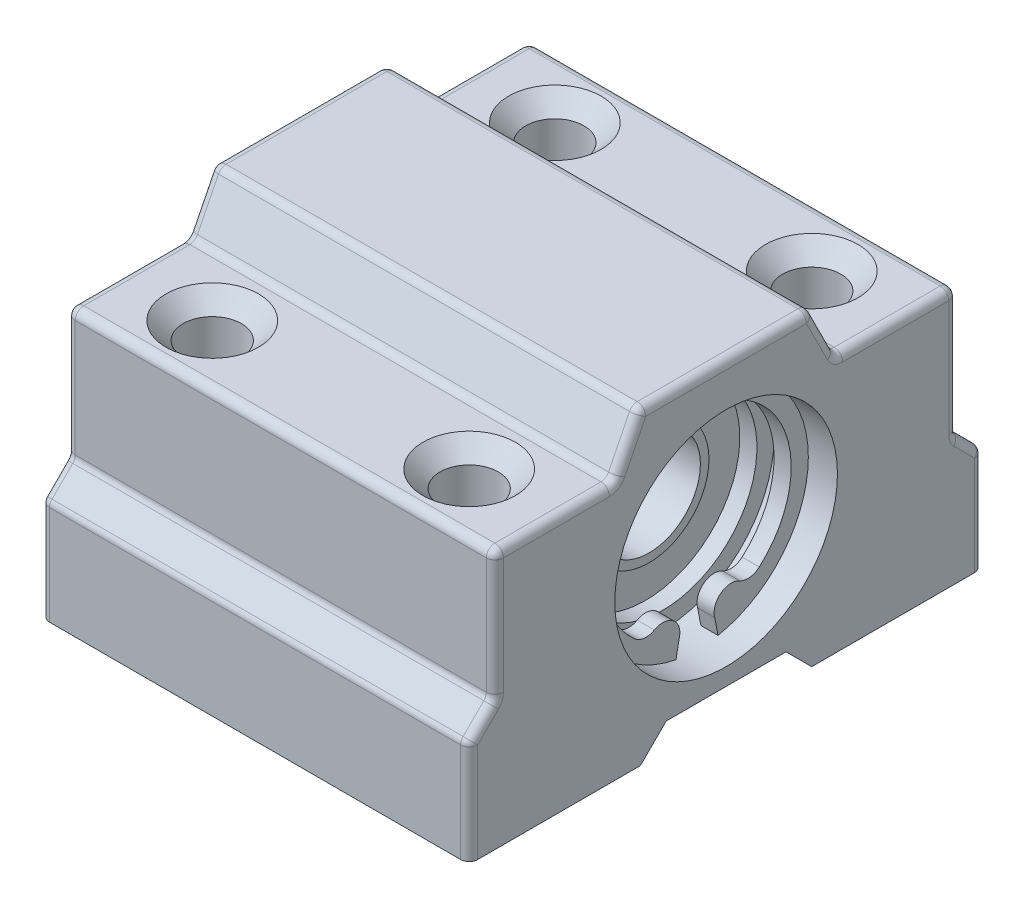
SolidWorks part; units mm, degrees
ref_plane "Front Plane" through (0, 0, 0) normal (0, 0, 1) x (1, 0, 0)
ref_plane "Top Plane" through (0, 0, 0) normal (0, 1, 0) x (1, 0, 0)
ref_plane "Right Plane" through (0, 0, 0) normal (1, 0, 0) x (0, 0, -1)
sketch "Sketch1" plane through (0, 0, 0) normal (1, 0, 0) x (0, 0, -1)
  line L1 (-5, -9) -> (-3.5, -7.5)
  line L2 (-3.5, -7.5) -> (3.5, -7.5)
  line L3 (3.5, -7.5) -> (5, -9)
  line L4 (5, -9) -> (15, -9)
  line L6 (15, -3) -> (13.5, -1.5)
  line L8 (13.5, 6) -> (6.5, 6)
  line L9 (6.5, 6) -> (5, 9)
  line L10 (5, 9) -> (-5, 9)
  line L11 (-5, 9) -> (-6.5, 6)
  line L12 (-6.5, 6) -> (-13.5, 6)
  line L15 (-15, -3) -> (-15, -9)
  line L16 (0, -7.5) -> (0, 9) construction
  line L17 (-16.278, 0) -> (14.0247, 0) construction
  line L18 (-15, -9) -> (-5, -9)
  line L19 (15, -3) -> (15, -9)
  line L20 (-13.5, -1.5) -> (-13.5, 6)
  line L21 (13.5, -1.5) -> (13.5, 6)
  line L22 (-10, 6) -> (-10, -9) construction
  line L23 (-10, -9) -> (10, 6) construction
  line L24 (10, 6) -> (10, -9) construction
  line L25 (-15, -3) -> (-13.5, -1.5)
  circle A0 centre (0, 0) radius 6.5
  circle A1 centre (0, 0) radius 5.5
  circle A2 centre (0, 0) radius 3
  point P18 (0, 9)
  dimension "D1" = 30
  dimension "D9" = 1.5
  dimension "D3" = 9
  dimension "D13" = 13
  dimension "D12" = 6
  dimension "D2" = 15
  dimension "D4" = 6
  dimension "D5" = 18
  dimension "D6" = 20
  dimension "D7" = 1.5
  dimension "D8" = 10
  dimension "D10" = 10
  dimension "D11" = 1
extrude "Boss-Extrude1" add sketch "Sketch1" along normal blind 25 contours L25 L15 L18 L1 L2 L3 L4 L19 L6 L21 L8 L9 L10 L11 L12 L20 A0 region at (0, -8.6501, 10)
extrude "Extrude-Thin1" add sketch "Sketch1<4>" along normal blind 20 from offset 0.5 separate body thin contours A2 thin type one direction wall 0.5
sketch "Sketch1<4>" plane through (0, 0, 0) normal (1, 0, 0) x (0, 0, -1) same geometry as "Sketch1"
extrude "Boss-Extrude2" add sketch "Sketch1<5>" along normal blind 19.5 from offset 0.8 contours A1 A2 region at (0, 0, 5.3444)
sketch "Sketch1<5>" plane through (0, 0, 0) normal (1, 0, 0) x (0, 0, -1) same geometry as "Sketch1"
extrude "Boss-Extrude3" add sketch "Sketch1<6>" along normal blind 21 from offset 0.3 contours A0 A1 region at (0, 0, 6.3162)
sketch "Sketch1<6>" plane through (0, 0, 0) normal (1, 0, 0) x (0, 0, -1) same geometry as "Sketch1"
ref_plane "Plane1" through (21.3, 0, 0) normal (1, 0, 0) x (0, 0, -1)
sketch "Sketch3" plane through (21.3, 0, 0) normal (1, 0, 0) x (0, 0, -1)
  line L0 (0, 0) -> (0, -50000) construction
  line L1 (-1.0393, -5.4009) -> (-1.2282, -6.3829)
  line L2 (1.0393, -5.4009) -> (1.2282, -6.3829)
  circle A0 centre (0, 0) radius 6.5 construction
  arc A1 (1.2282, -6.3829) -> (-1.2282, -6.3829) centre (0, 0) ccw
  circle A2 centre (0, 0) radius 5.5 construction
  arc A3 (0, -5.5) -> (1.0393, -5.4009) centre (0, 0) ccw
  arc A4 (-1.0393, -5.4009) -> (-2.4872, -4.2502) centre (-2, -5.1235) ccw
  circle A5 centre (-2, -5.1235) radius 0.25
  arc A6 (-2.2308, -5.0273) -> (-1.7651, -5.2091) centre (0, 0) ccw
  arc A7 (-2.4872, -4.2502) -> (-3.6353, -4.1273) centre (-2.9744, -3.3769) cw
  arc A8 (2.4872, -4.2502) -> (3.6353, -4.1273) centre (2.9744, -3.3769) ccw
  circle A10 centre (2, -5.1235) radius 0.25
  arc A11 (1.0393, -5.4009) -> (2.4872, -4.2502) centre (2, -5.1235) cw
  arc A13 (3.6353, -4.1273) -> (-3.6353, -4.1273) centre (0, 0) ccw
  dimension "D1" = 0.5
  dimension "D2" = 2
  dimension "D3" = 1
  dimension "D4" = 2
extrude "Boss-Extrude4" add sketch "Sketch3" along normal blind 1 from offset 1 contours A11 A8 A13 A7 A4 L1 A1 L2
fillet "Fillet1" radius 0.5 32 edges at (12.5, -1.5, -13.5) (12.5, -1.5, 13.5) (12.5, -3, 15) (12.5, -3, -15) (12.5, 6, -6.5) (12.5, 6, 6.5) (12.5, 9, 5) (12.5, 9, -5) (12.5, 6, -13.5) (12.5, 6, 13.5) (25, 7.5, -5.75) (25, 7.5, 5.75) (25, 2.25, 13.5) (0, -2.25, 14.25) (0, 7.5, 5.75) (25, -2.25, -14.25) (25, -6, -15) (25, 2.25, -13.5) (25, 9, 0) (25, 6, -10) (25, 6, 10) (25, -2.25, 14.25) (25, -6, 15) (0, -6, -15) (0, -2.25, -14.25) (0, 2.25, -13.5) (0, 7.5, -5.75) (0, 6, -10) (0, 9, 0) (0, -6, 15) (0, 2.25, 13.5) (0, 6, 10)
sketch "Sketch4" plane through (0, -9, 0) normal (0, -1, 0) x (1, 0, 0)
  line L0 (12.5, 15) -> (12.5, -15) construction
  line L1 (24.5, 15) -> (0.5, 15) construction
  line L2 (24.5, -15) -> (0.5, -15) construction
  line L4 (-4.9444, 10) -> (27.0918, 10) construction
  line L6 (0, 0) -> (36.1646, 0) construction
  circle A0 centre (5, 10) radius 1.7
  circle A1 centre (20, 10) radius 1.7
  circle A2 centre (20, -10) radius 1.7
  circle A3 centre (5, -10) radius 1.7
  dimension "D2" = 3.4
  dimension "D3" = 15
  dimension "D1" = 10
extrude "Cut-Extrude3" cut sketch "Sketch4" against normal through all
chamfer "Chamfer1" distance 1 angle 45 6 edges at (20, 6, -11.7) (5, 6, -11.7) (5, 6, 8.3) (20, 6, 8.3) (20, -9, 11.7) (5, -9, 8.3)
